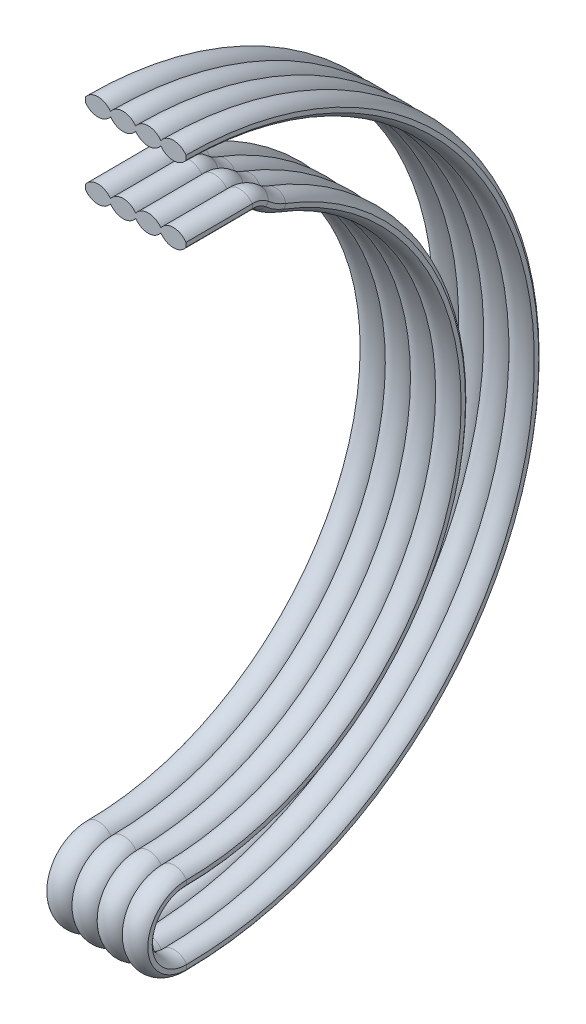
SolidWorks part; units mm, degrees
ref_plane "Front Plane" through (0, 0, 0) normal (0, 0, 1) x (1, 0, 0)
ref_plane "Top Plane" through (0, 0, 0) normal (0, 1, 0) x (1, 0, 0)
ref_plane "Right Plane" through (0, 0, 0) normal (1, 0, 0) x (0, 0, -1)
sketch "Sketch1" plane through (0, 0, 0) normal (0, 0, 1) x (1, 0, 0)
  line L0 (-117.2472, 0) -> (-83.3707, 0) construction
  line L1 (-24.5288, 0.4445) -> (22.9896, 0.4445) construction
  line L2 (-1.905, 1.7956) -> (-1.905, -0.3269) construction
  line L3 (-2.54, 0.1111) -> (-1.27, 0.1111) construction
  line L4 (-2.54, 0.1111) -> (-2.54, -0.1111)
  line L5 (0, -1.8178) -> (0, -0.6618) construction
  line L6 (2.54, 0.1111) -> (2.54, -0.1111)
  arc A0 (-2.54, 0.1111) -> (-1.27, 0.1111) centre (-1.905, -0.3269) cw
  arc A1 (-2.54, -0.1111) -> (-1.27, -0.1111) centre (-1.905, 0.3269) ccw
  arc A2 (-1.27, 0.1111) -> (0, 0.1111) centre (-0.635, -0.3269) cw
  arc A3 (-1.27, -0.1111) -> (0, -0.1111) centre (-0.635, 0.3269) ccw
  arc A4 (0, 0.1111) -> (1.27, 0.1111) centre (0.635, -0.3269) cw
  arc A5 (0, -0.1111) -> (1.27, -0.1111) centre (0.635, 0.3269) ccw
  arc A6 (1.27, 0.1111) -> (2.54, 0.1111) centre (1.905, -0.3269) cw
  arc A7 (1.27, -0.1111) -> (2.54, -0.1111) centre (1.905, 0.3269) ccw
  dimension "D1" = 0.4445
  dimension "D2" = 0.1111
  dimension "D3" = 0.635
  dimension "D5" = 1.905
  dimension "D4" = 4
sketch "Sketch2" plane through (0, 0, 0) normal (1, 0, 0) x (0, 0, -1)
  line L0 (0, -200001.8178) -> (0, 199999.3382) construction
  line L1 (0, 0) -> (0.7728, 0) construction
  arc A0 (5, -0.8121) -> (0.0301, -27.8888) centre (0, -13.8888) cw
  arc A1 (-2.4444, 5.9612) -> (2.6555, 5.9341) centre (0, -13.8888) ccw construction
  arc A2 (0.0301, -27.8888) -> (0.0381, -31.5888) centre (0.0341, -29.7388) ccw
  arc A3 (0.0381, -31.5888) -> (0, 3.8112) centre (0, -13.8888) ccw
  arc A4 (-3.2323, -0.7815) -> (3.2323, -0.7815) centre (0, -13.8888) ccw construction
  arc A5 (-2.4444, 5.9612) -> (2.6555, 5.9341) centre (0, -13.8888) ccw construction
  arc A6 (-3.2323, -0.7815) -> (3.2323, -0.7815) centre (0, -13.8888) ccw construction
  arc A7 (0, 0) -> (3.3466, 0.017) centre (0, 329.2596) ccw
  arc A8 (3.3466, 0.017) -> (4.0879, -0.2595) centre (3.3578, -1.0848) cw
  arc A9 (4.0879, -0.2595) -> (5, -0.8121) centre (6.0665, 1.9772) ccw
  circle A10 centre (0, -13.8888) radius 17.7 construction
  dimension "D1" = 14
  dimension "D3" = 25.4
  dimension "D2" = 5
sweep "Sweep2" add profiles "Sketch1" path "Sketch2"
equation "\"Pitch\"= 0.05in"
equation "\"height\"= 0.035in"
equation "\"NumConnectors\"= int ( 4 )"
equation "\"D1@Sketch1\"=\"height\"/2"
equation "\"D2@Sketch1\"=\"height\"/8"
equation "\"D3@Sketch1\"=\"Pitch\"/2"
equation "\"D4@Sketch1\"=int(\"NumConnectors\")"
equation "\"D5@Sketch1\"=\"Pitch\"*(\"NumConnectors\"-1)/2"
equation "\"BearingBaseDistance\"= 12"
equation "\"BearingOD\"= 32"
equation "\"BearingID\" = 25"
equation "\"BearingHeight\"= 4"
equation "\"SeatsOD\"= \"BearingOD\" + 10"
equation "\"WireHarnessHeight\"= 4"
equation "\"OuterWallWidth\"= 5"
equation "\"OverallOD\" = 40"
equation "\"OuterHousingHeight\" = \"WireHarnessHeight\" + \"BearingHeight\"*2 + \"BearingBaseDistance\""
equation "\"RetainingRingThickness\" = 1.30"
equation "\"RetaininRingGrooveDiameter\" = 23.9"
equation "\"ShaftLengthAfterFlange\" = 2*\"BearingHeight\" + \"BearingBaseDistance\" + \"RetainingRingThickness\"*2 'give a retaining ring thickness of extra clearance"
equation "\"RetainingRingGrooveBase\" = \"ShaftLengthAfterFlange\" - \"RetainingRingThickness\"*2"
equation "\"CoverThickness\" = 1"
equation "\"CoverClearance\" = 1"
equation "\"FlangHeight\" = \"CoverThickness\" + \"CoverClearance\" + \"WireHarnessHeight\""
equation "\"PCBWidth\" = 5"
equation "\"PCBHeight\" = \"OuterHousingHeight\" "
equation "\"PCBThickness\" = 1"
equation "\"NormalDistSidewallPCBToZ\" = (\"OverallOD\"/2) - 1.6 'radial distance from the z axis to pcb origin on the top/connector side"
equation "\"PCBSidewallCutoutClearance\" = 0.1"
equation "\"OutputHubBoltCircleRadius\" = 8"
equation "\"OutputHubOD\" = 27"
equation "\"StatorWireRadius\" = \"NormalDistSidewallPCBToZ\" - 5.7"
equation "\"D3@Sketch2\"=\"StatorWireRadius\"*2"
